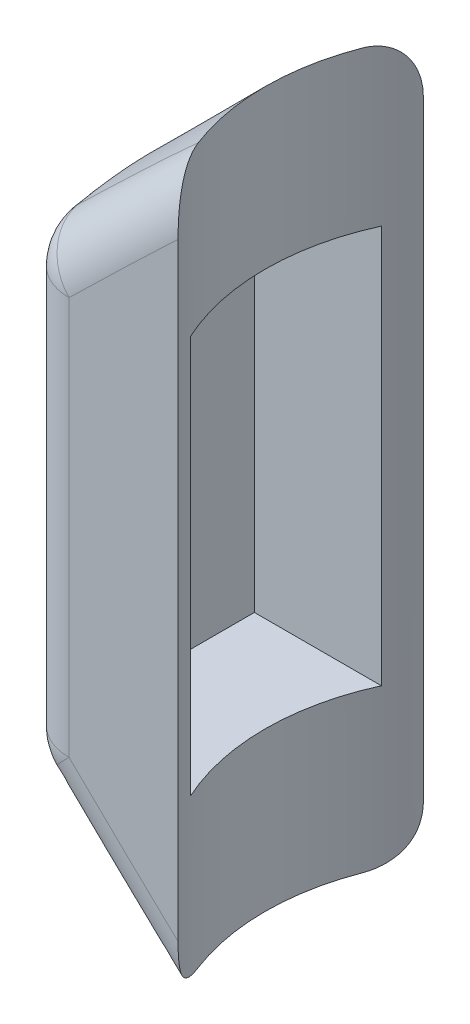
SolidWorks part; units mm, degrees
ref_plane "Front Plane" through (0, 0, 0) normal (0, 0, 1) x (1, 0, 0)
ref_plane "Top Plane" through (0, 0, 0) normal (0, 1, 0) x (1, 0, 0)
ref_plane "Right Plane" through (0, 0, 0) normal (1, 0, 0) x (0, 0, -1)
sketch "Sketch1" plane through (0, 0, 0) normal (0, 1, 0) x (1, 0, 0)
  circle A0 centre (0, 0) radius 42
  circle A1 centre (0, 0) radius 39
  dimension "D1" = 84
  dimension "D2" = 3
extrude "Boss-Extrude1" add sketch "Sketch1" along normal blind 750
ref_plane "Plane1" through (0, 650, 0) normal (0, 1, 0) x (1, 0, 0)
sketch "Sketch2" plane through (0, 650, 0) normal (0, 1, 0) x (1, 0, 0)
  line L0 (-42, 0) -> (-65.4648, 0) construction
  line L1 (-65.4648, -22.5) -> (-65.4648, 22.5)
  line L2 (-65.4648, 22.5) -> (-35.4648, 22.5)
  line L3 (-65.4648, -22.5) -> (-35.4648, -22.5)
  circle A0 centre (0, 0) radius 42 construction
  arc A1 (-35.4648, 22.5) -> (-35.4648, -22.5) centre (0, 0) ccw
  dimension "D1" = 30
  dimension "D2" = 45
extrude "Boss-Extrude2" add sketch "Sketch2" against normal blind 75 contours A1 L3 L1 L2
sketch "Sketch3" plane through (0, 750, 0) normal (0, 1, 0) x (1, 0, 0)
  circle A0 centre (0, 0) radius 39 construction
  circle A1 centre (0, 0) radius 42
  circle A2 centre (0, 0) radius 42
  circle A3 centre (0, 0) radius 39
  dimension "D1" = 0
chamfer "Chamfer1" distance 28 angle 45 1 edges at (-42, 650, 0)
chamfer "Chamfer2" distance 28 angle 45 1 edges at (-42, 575, 0)
fillet "Fillet1" radius 10 8 edges at (-65.4648, 570.5083, -2.3883) (-65.4648, 612.5, -22.5) (-65.4648, 612.5, 22.5) (-65.4648, 654.4917, 2.3883)
sketch "Sketch6" plane through (0, 750, 0) normal (0, 1, 0) x (1, 0, 0)
  circle A0 centre (0, 0) radius 39 construction
  circle A1 centre (0, 0) radius 42
  circle A2 centre (0, 0) radius 42
  circle A3 centre (0, 0) radius 39
  dimension "D1" = 0
sketch "Sketch9" plane through (0, 750, 0) normal (0, 1, 0) x (1, 0, 0)
  circle A0 centre (0, 0) radius 39 construction
  circle A1 centre (0, 0) radius 42
  circle A2 centre (0, 0) radius 42
  circle A3 centre (0, 0) radius 39
  dimension "D1" = 0
extrude "Cut-Extrude3" cut sketch "Sketch9" against normal through all
ref_plane "Plane3" through (-35.4648, 0, 0) normal (-1, 0, 0) x (0, 0, 1)
sketch "Sketch10" plane through (-35.4648, 0, 0) normal (-1, 0, 0) x (0, 0, 1)
  line L0 (0, 678) -> (0, 547) construction
  line L1 (-15.0305, 678) -> (15.0305, 678) construction
  line L6 (15.0305, 547) -> (-15.0305, 547) construction
  line L8 (-17.5, 649) -> (17.5, 649)
  line L9 (-17.5, 649) -> (-17.5, 576)
  line L10 (-17.5, 576) -> (17.5, 576)
  line L11 (17.5, 649) -> (17.5, 576)
  line L12 (-17.5, 649) -> (17.5, 576) construction
  line L13 (-17.5, 576) -> (17.5, 649) construction
  point P9 (0, 612.5)
  dimension "D1" = 35
  dimension "D2" = 73
extrude "Cut-Extrude4" cut sketch "Sketch10" along normal blind 26
sketch "Sketch12" plane through (0, 0, -17.5) normal (0, 0, 1) x (1, 0, 0)
  line L4 (-38.1805, 576) -> (-38.1805, 649)
  line L5 (-38.1805, 649) -> (-61.4648, 649)
  line L6 (-61.4648, 649) -> (-61.4648, 576)
  line L7 (-61.4648, 576) -> (-38.1805, 576)
  line L8 (-38.1805, 576) -> (-38.1805, 649)
  line L9 (-38.1805, 649) -> (-61.4648, 649)
  line L10 (-61.4648, 649) -> (-61.4648, 576)
  line L11 (-61.4648, 576) -> (-38.1805, 576)
  dimension "D1" = 0
